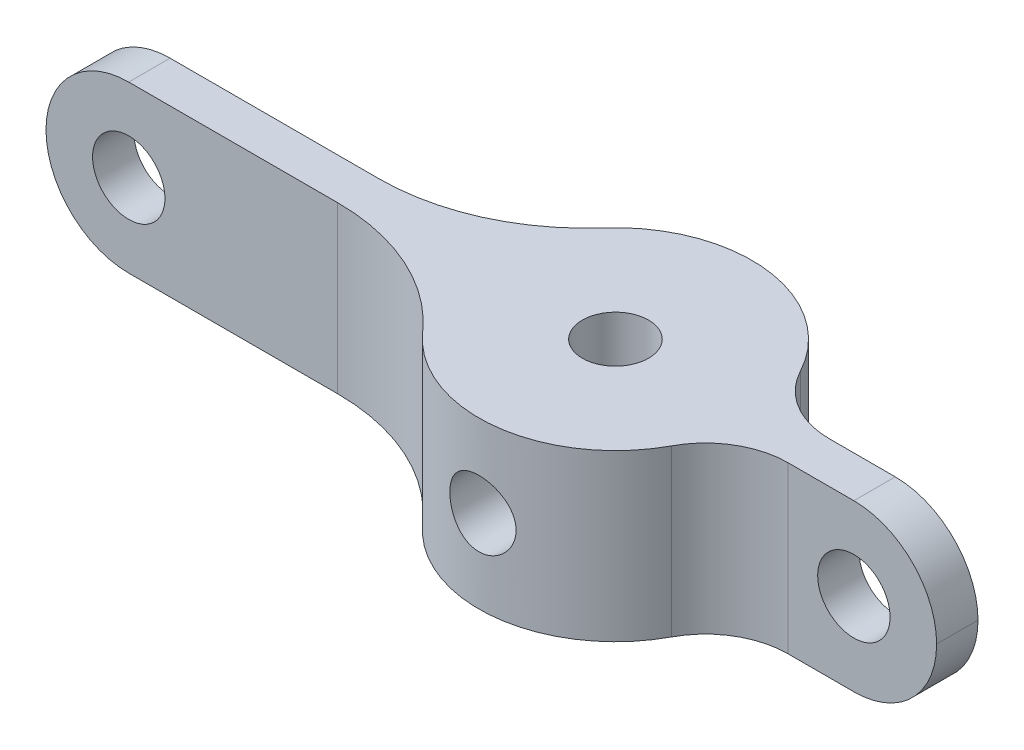
SolidWorks part; units mm, degrees
ref_plane "Front Plane" through (0, 0, 0) normal (0, 0, 1) x (1, 0, 0)
ref_plane "Top Plane" through (0, 0, 0) normal (0, 1, 0) x (1, 0, 0)
ref_plane "Right Plane" through (0, 0, 0) normal (1, 0, 0) x (0, 0, -1)
sketch "Sketch1" plane through (0, 0, 0) normal (0, 1, 0) x (1, 0, 0)
  line L0 (0, 0) -> (0, 8.3213) construction
  line L1 (-26.5238, 1) -> (-6.5238, 1)
  line L2 (-26.5238, 1) -> (-26.5238, -1)
  line L3 (-26.5238, -1) -> (-6.5238, -1)
  line L5 (0, 0) -> (-26.5238, 0) construction
  line L7 (6.5238, 1) -> (16.5238, 1)
  line L9 (6.5238, -1) -> (16.5238, -1)
  line L10 (16.5238, 1) -> (16.5238, -1)
  circle A0 centre (0, 0) radius 1.6
  arc A1 (-6.5238, -1) -> (6.5238, -1) centre (0, 0) ccw
  circle A2 centre (0, 0) radius 6.6 construction
  arc A3 (6.5238, 1) -> (-6.5238, 1) centre (0, 0) ccw
  arc A4 (-6.5238, -1) -> (6.5238, -1) centre (0, 0) ccw
  arc A5 (6.5238, 1) -> (-6.5238, 1) centre (0, 0) ccw
  dimension "D1" = 3.2
  dimension "D3" = 2
  dimension "D4" = 20
  dimension "D5" = 10
  dimension "D2" = 5
extrude "Boss-Extrude1" add sketch "Sketch1" along normal blind 8 contours A1 A4 A3 L1 L2 L3 A0 region at (-2.2825, 0, 0)
sketch "Sketch2" plane through (0, 0, 1) normal (0, 0, 1) x (1, 0, 0)
  line L0 (-26.5238, 4) -> (-22.5238, 4) construction
  line L1 (16.5238, 8) -> (16.5238, 0) construction
  line L2 (6.5238, 8) -> (16.5238, 8) construction
  line L3 (-26.5238, 8) -> (-26.5238, 0) construction
  line L4 (12.5238, 0) -> (16.5238, 0)
  line L5 (16.5238, 0) -> (16.5238, 8)
  line L6 (0, 0) -> (0, 10.8746) construction
  line L7 (-6.5238, 0) -> (-6.5238, 8)
  line L8 (-22.5238, 4) -> (0, 4) construction
  line L9 (-6.5238, 0) -> (-6.5238, 8)
  line L10 (16.5238, 8) -> (12.5238, 8)
  line L11 (-22.5238, 8) -> (-22.5238, 4) construction
  line L13 (6.5238, 0) -> (16.5238, 0)
  line L14 (16.5238, 0) -> (16.5238, 8)
  line L15 (16.5238, 8) -> (6.5238, 8)
  line L16 (-26.5238, 0) -> (-6.5238, 0)
  line L17 (6.5238, 8) -> (6.5238, 0)
  line L18 (-6.5238, 8) -> (-26.5238, 8)
  line L19 (-26.5238, 8) -> (-26.5238, 0)
  line L20 (-26.5238, 0) -> (-22.5238, 0)
  line L22 (-22.5238, 8) -> (-26.5238, 8)
  line L23 (-26.5238, 8) -> (-26.5238, 0)
  line L24 (6.5238, 0) -> (16.5238, 0)
  line L25 (16.5238, 0) -> (16.5238, 8)
  line L26 (16.5238, 8) -> (12.5238, 8)
  circle A0 centre (-22.5238, 4) radius 1.75
  circle A2 centre (0, 4) radius 1.6
  arc A3 (-22.5238, 8) -> (-22.5238, 0) centre (-22.5238, 4) ccw
  circle A4 centre (12.5238, 4) radius 1.75
  arc A5 (12.5238, 0) -> (12.5238, 8) centre (12.5238, 4) ccw
  line M9 (-26.5238, 8) -> (-26.5238, 0)
  line M12 (-26.5238, 0) -> (-6.5238, 0)
  line M13 (-6.5238, 8) -> (-26.5238, 8)
  dimension "D1" = 3.5
  dimension "D2" = 3.2
  dimension "D3" = 0
  dimension "D4" = 0
extrude "Cut-Extrude1" cut sketch "Sketch2" against normal through all both and the other way through all contours A3 M13 M9 | A3 L23 M12 | A0 | A2 | A4 region at (-25.6303, 0.8935, 1) region at (-25.6303, 7.1065, 1) region at (-22.5238, 4, 1) region at (0, 4, 1)
fillet "Fillet1" radius 10 2 edges at (-6.5238, 4, -1) (-6.5238, 4, 1)
fillet "Fillet2" radius 4 2 edges at (16.5238, 0, 0) (16.5238, 8, 0)
fillet "Fillet3" radius 4 2 edges at (6.5238, 4, -1) (6.5238, 4, 1)
